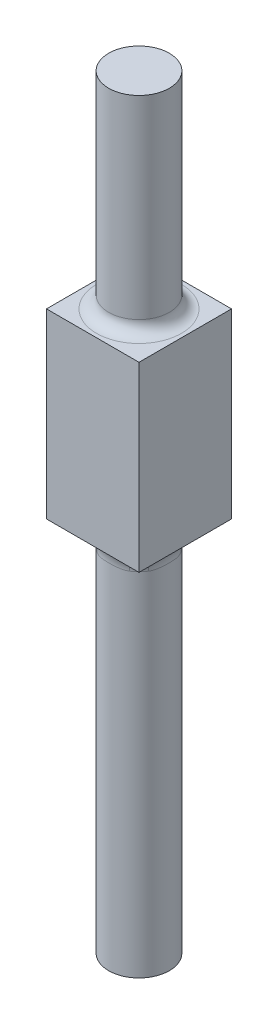
SolidWorks part; units mm, degrees
ref_plane "Front Plane" through (0, 0, 0) normal (0, 0, 1) x (1, 0, 0)
ref_plane "Top Plane" through (0, 0, 0) normal (0, 1, 0) x (1, 0, 0)
ref_plane "Right Plane" through (0, 0, 0) normal (1, 0, 0) x (0, 0, -1)
sketch "Sketch1" plane through (0, 0, 0) normal (0, 1, 0) x (1, 0, 0)
  circle A0 centre (0, 0) radius 5
  dimension "D1" = 10
extrude "Boss-Extrude1" add sketch "Sketch1" along normal blind 62
sketch "Sketch3" plane through (0, 62, 0) normal (0, 1, 0) x (1, 0, 0)
  line L1 (-7.625, -7.625) -> (7.625, -7.625)
  line L2 (-7.625, -7.625) -> (-7.625, 7.625)
  line L3 (-7.625, 7.625) -> (7.625, 7.625)
  line L4 (7.625, -7.625) -> (7.625, 7.625)
  line L5 (-7.625, -7.625) -> (7.625, 7.625) construction
  line L6 (-7.625, 7.625) -> (7.625, -7.625) construction
  point P0 (0, 0)
  dimension "D1" = 15.25
  dimension "D2" = 15.25
extrude "Boss-Extrude2" add sketch "Sketch3" along normal blind 30
sketch "Sketch4" plane through (0, 92, 0) normal (0, 1, 0) x (1, 0, 0)
  circle A0 centre (0, 0) radius 5
  dimension "D1" = 10
sketch "Sketch5" plane through (0, 0, 0) normal (0, -1, 0) x (1, 0, 0)
  circle A0 centre (0, 0) radius 3
  dimension "D1" = 6
extrude "Cut-Extrude1" cut sketch "Sketch5" against normal blind 10
fillet "Fillet1" radius 4 1 edges at (0, 62, 5)
extrude "Boss-Extrude3" add sketch "Sketch4" along normal blind 34
fillet "Fillet2" radius 2 1 edges at (0, 92, 5)
